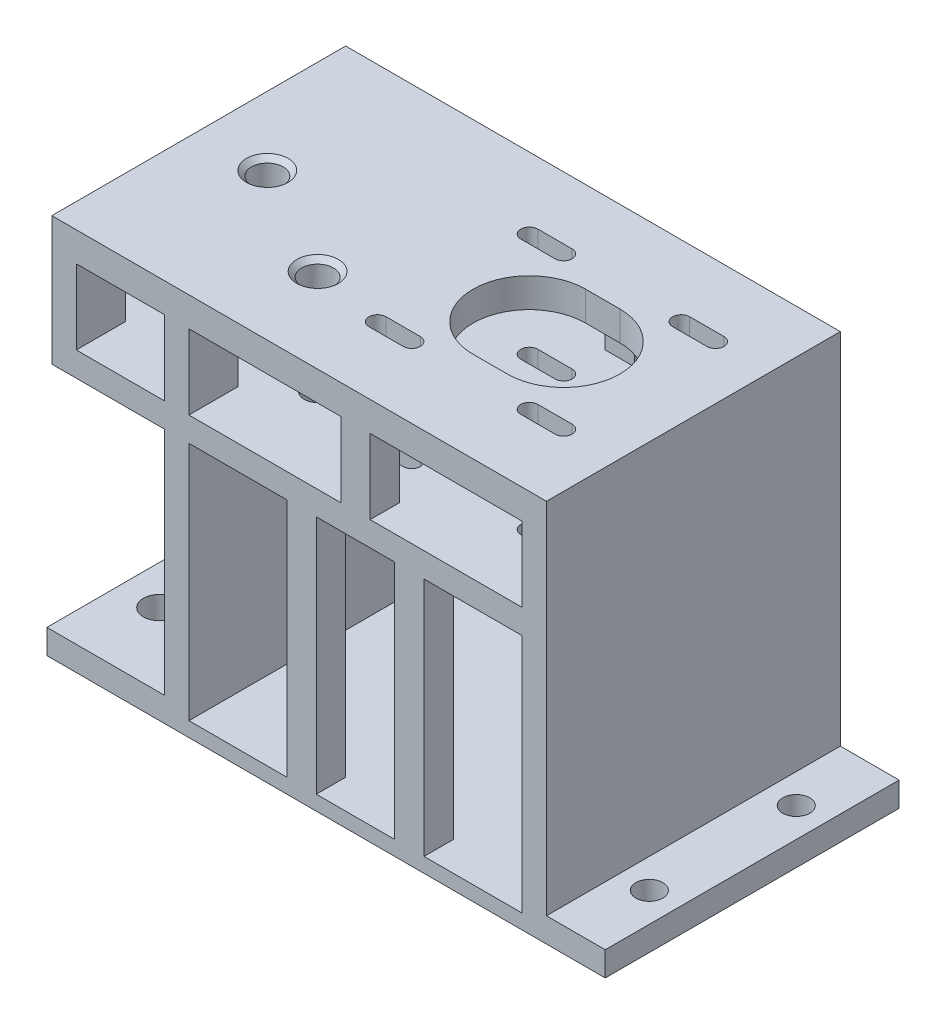
SolidWorks part; units mm, degrees
material "PET"
ref_plane "Front Plane" through (0, 0, 0) normal (0, 0, 1) x (1, 0, 0)
ref_plane "Top Plane" through (0, 0, 0) normal (0, 1, 0) x (1, 0, 0)
ref_plane "Right Plane" through (0, 0, 0) normal (1, 0, 0) x (0, 0, -1)
sketch "Sketch1" plane through (0, 0, 0) normal (0, 0, 1) x (1, 0, 0)
  line L0 (85, 0) -> (-29, 0)
  line L1 (-29, 0) -> (-29, 5)
  line L2 (-29, 5) -> (-5, 5)
  line L3 (-5, 5) -> (-5, 52.05)
  line L6 (-28, 78.3) -> (73, 78.3)
  line L7 (73, 78.3) -> (73, 5)
  line L11 (68, 3) -> (68, 52.05)
  line L12 (68, 72.3) -> (0, 72.3)
  line L13 (0, 72.3) -> (0, 57.05)
  line L14 (0, 57.05) -> (68, 57.05)
  line L16 (68, 52.05) -> (0, 52.05)
  line L17 (0, 3) -> (0, 52.05)
  line L19 (-28, 78.3) -> (-28, 52.05)
  line L20 (-28, 52.05) -> (-5, 52.05)
  line L21 (-5, 72.3) -> (-23, 72.3)
  line L22 (-23, 72.3) -> (-23, 57.05)
  line L23 (-23, 57.05) -> (-5, 57.05)
  line L25 (-5, 57.05) -> (-5, 72.3)
  line L28 (68, 57.05) -> (68, 72.3)
  line L29 (73, 5) -> (85, 5)
  line L30 (85, 5) -> (85, 0)
  line L31 (0, 3) -> (68, 3)
  point P19 (0, 27.525)
  point P28 (-29, 2.5)
  dimension "D1" = 5
  dimension "D2" = 6
  dimension "D3" = 5
  dimension "D4" = 5
  dimension "D5" = 5
  dimension "D6" = 15.25
  dimension "D7" = 57.05
  dimension "D8" = 101
  dimension "D9" = 5
  dimension "D10" = 12
  dimension "D11" = 3
  dimension "D13" = 23
  dimension "D14" = 5
  dimension "D15" = 5
  dimension "D16" = 24
extrude "Boss-Extrude1" add sketch "Sketch1" along normal blind 60
sketch "Sketch2" plane through (0, 0, 0) normal (1, 0, 0) x (0, 0, -1)
  line L0 (-60, 5) -> (-60, 78.3) construction
  line L1 (-50, 72.3) -> (-10, 72.3)
  line L2 (-50, 72.3) -> (-50, 57.05)
  line L3 (-50, 57.05) -> (-10, 57.05)
  line L4 (-10, 72.3) -> (-10, 57.05)
  line L5 (-60, 78.3) -> (0, 78.3) construction
  line L6 (0, 5) -> (0, 78.3) construction
  dimension "D1" = 10
  dimension "D2" = 15.25
  dimension "D3" = 6
  dimension "D4" = 10
extrude "Cut-Extrude1" cut sketch "Sketch2" against normal through all
sketch "Sketch3" plane through (0, 78.3, 0) normal (0, 1, 0) x (1, 0, 0)
  line L0 (18, -30) -> (68, -30) construction
  line L2 (73, -60) -> (73, 0) construction
  line L3 (39.5, -30) -> (46.5, -30) construction
  line L4 (39.5, -18.5) -> (46.5, -18.5)
  line L5 (39.5, -41.5) -> (46.5, -41.5)
  line L6 (31, -14.5) -> (24, -14.5) construction
  line L7 (31, -16.25) -> (24, -16.25)
  line L8 (31, -12.75) -> (24, -12.75)
  line L9 (43, -30) -> (43, 0) construction
  line L10 (73, -60) -> (-28, -60) construction
  line L12 (73, 0) -> (-28, 0) construction
  line L13 (55, -14.5) -> (62, -14.5) construction
  line L14 (55, -16.25) -> (62, -16.25)
  line L15 (55, -12.75) -> (62, -12.75)
  line L16 (31, -45.5) -> (24, -45.5) construction
  line L17 (31, -43.75) -> (24, -43.75)
  line L18 (31, -47.25) -> (24, -47.25)
  line L19 (55, -45.5) -> (62, -45.5) construction
  line L20 (55, -43.75) -> (62, -43.75)
  line L21 (55, -47.25) -> (62, -47.25)
  arc A0 (39.5, -18.5) -> (39.5, -41.5) centre (39.5, -30) ccw
  arc A1 (46.5, -41.5) -> (46.5, -18.5) centre (46.5, -30) ccw
  arc A2 (31, -16.25) -> (31, -12.75) centre (31, -14.5) ccw
  arc A3 (24, -12.75) -> (24, -16.25) centre (24, -14.5) ccw
  arc A4 (55, -16.25) -> (55, -12.75) centre (55, -14.5) cw
  arc A5 (62, -12.75) -> (62, -16.25) centre (62, -14.5) cw
  arc A6 (31, -43.75) -> (31, -47.25) centre (31, -45.5) cw
  arc A7 (24, -47.25) -> (24, -43.75) centre (24, -45.5) cw
  arc A8 (55, -43.75) -> (55, -47.25) centre (55, -45.5) ccw
  arc A9 (62, -47.25) -> (62, -43.75) centre (62, -45.5) ccw
  point P8 (43, -30)
  point P15 (27.5, -14.5)
  point P24 (58.5, -14.5)
  point P31 (27.5, -45.5)
  point P38 (58.5, -45.5)
  dimension "D2" = 11.5
  dimension "D4" = 1.75
  dimension "D1" = 7
  dimension "D3" = 7
  dimension "D5" = 15.5
  dimension "D6" = 15.5
  dimension "D7" = 5
  dimension "D8" = 55
  dimension "D9" = 30
extrude "Cut-Extrude2" cut sketch "Sketch3" against normal up to surface (26.25 mm away) up to face at (34, 52.05, 30)
sketch "Sketch5" plane through (0, 78.3, 0) normal (0, 1, 0) x (1, 0, 0)
  line L0 (73, -30) -> (-28, -30) construction
  line L4 (73, -60) -> (73, 0) construction
  line L5 (-28, -60) -> (-28, 0) construction
  circle A0 centre (9, -42.73) radius 3.25
  dimension "D1" = 6.5
  dimension "D3" = 64
  dimension "D2" = 12.73
extrude "Cut-Extrude3" cut sketch "Sketch5" against normal up to next
sketch "Sketch6" plane through (0, 57.05, 0) normal (0, 1, 0) x (1, 0, 0)
  circle A0 centre (9, -42.73) radius 2.75
  dimension "D1" = 5.5
extrude "Cut-Extrude4" cut sketch "Sketch6" against normal up to next
sketch "Sketch7" plane through (0, 78.3, 0) normal (0, 1, 0) x (1, 0, 0)
  line L0 (28, -30) -> (-29, -30) construction
  line L3 (-29, -60) -> (-29, 0) construction
  line L4 (-28, -60) -> (-28, 0) construction
  arc A0 (39.5, -18.5) -> (39.5, -41.5) centre (39.5, -30) ccw construction
  circle A1 centre (-14, -30) radius 2.75
  dimension "D1" = 14
  dimension "D2" = 5.5
extrude "Cut-Extrude5" cut sketch "Sketch7" against normal through all
sketch "Sketch8" plane through (0, 78.3, 0) normal (0, 1, 0) x (1, 0, 0)
  circle A0 centre (-14, -30) radius 3.25
  dimension "D1" = 6.5
extrude "Cut-Extrude6" cut sketch "Sketch8" against normal up to next
chamfer "Chamfer1" distance 1 angle 45 2 edges at (-14, 78.3, 33.25) (9, 78.3, 45.98)
ref_plane "Plane1" through (9, 0, 0) normal (1, 0, 0) x (0, 0, -1)
sketch "Sketch10" plane through (0, 0, 0) normal (0, -1, 0) x (1, 0, 0)
  line L0 (-21, 60) -> (-21, 0) construction
  line L1 (-29, 60) -> (85, 60) construction
  line L2 (-29, 0) -> (85, 0) construction
  line L3 (79, 60) -> (79, 0) construction
  line L6 (0, 60) -> (0, 0) construction
  line L7 (-21, 45) -> (79, 45) construction
  line L8 (-29, 30) -> (85, 30) construction
  line L9 (-29, 60) -> (-29, 0) construction
  line L11 (-21, 15) -> (79, 15) construction
  line L13 (85, 60) -> (85, 0) construction
  line L14 (-29, 0) -> (85, 0) construction
  line L15 (-29, 60) -> (85, 60) construction
  circle A0 centre (-21, 45) radius 3.3
  circle A1 centre (-21, 15) radius 3.3
  circle A2 centre (79, 15) radius 2.75
  circle A3 centre (79, 45) radius 2.75
  dimension "D5" = 6.6
  dimension "D6" = 6.6
  dimension "D7" = 5.5
  dimension "D8" = 5.5
  dimension "D1" = 21
  dimension "D2" = 15
  dimension "D3" = 15
  dimension "D4" = 6
extrude "Cut-Extrude8" cut sketch "Sketch10" against normal up to next
sketch "Sketch11" plane through (0, 52.05, 0) normal (0, -1, 0) x (1, 0, 0)
  line L0 (0, 60) -> (0, 0) construction
  line L1 (0, 38) -> (18.5, 38)
  line L2 (0, 38) -> (0, 22)
  line L3 (0, 22) -> (18.5, 22)
  line L4 (18.5, 38) -> (18.5, 22)
  line L5 (73, 30) -> (-28, 30) construction
  dimension "D1" = 5.5
  dimension "D2" = 8
  dimension "D3" = 16
extrude "Boss-Extrude2" add sketch "Sketch11" along normal blind 12
sketch "Sketch12" plane through (18.5, 0, 0) normal (1, 0, 0) x (0, 0, -1)
  line L0 (-38, 40.05) -> (-22, 52.05) construction
  circle A0 centre (-29.334, 46.5495) radius 3.25
  dimension "D1" = 6.5
extrude "Cut-Extrude9" cut sketch "Sketch12" against normal through all
chamfer "Chamfer2" distance 1 angle 45 1 edges at (-5, 46.5495, 26.084)
sketch "Sketch13" plane through (0, 0, 60) normal (0, 0, 1) x (1, 0, 0)
  line L0 (0, 57.05) -> (68, 57.05) construction
  line L1 (31, 72.3) -> (37, 72.3)
  line L2 (31, 72.3) -> (31, 57.05)
  line L3 (31, 57.05) -> (37, 57.05)
  line L4 (37, 72.3) -> (37, 57.05)
  dimension "D1" = 6
extrude "Boss-Extrude3" add sketch "Sketch13" against normal blind 6
sketch "Sketch14" plane through (0, 0, 60) normal (0, 0, 1) x (1, 0, 0)
  line L0 (68, 52.05) -> (0, 52.05) construction
  line L1 (20, 52.05) -> (26, 52.05)
  line L2 (20, 52.05) -> (20, 3)
  line L3 (20, 3) -> (26, 3)
  line L4 (26, 52.05) -> (26, 3)
  line L5 (0, 3) -> (68, 3) construction
  line L6 (0, 52.05) -> (0, 3) construction
  line L7 (42, 52.05) -> (48, 52.05)
  line L8 (42, 52.05) -> (42, 3)
  line L9 (42, 3) -> (48, 3)
  line L10 (48, 52.05) -> (48, 3)
  line L11 (68, 3) -> (68, 52.05) construction
  dimension "D1" = 6
  dimension "D2" = 6
  dimension "D3" = 20
  dimension "D4" = 20
extrude "Boss-Extrude4" add sketch "Sketch14" against normal blind 6
sketch "Sketch15" plane through (0, 0, 0) normal (0, 0, -1) x (-1, 0, 0)
  line L1 (-26, 52.05) -> (-20, 52.05)
  line L2 (-26, 52.05) -> (-26, 3)
  line L3 (-26, 3) -> (-20, 3)
  line L4 (-20, 52.05) -> (-20, 3)
  line L5 (-37, 57.05) -> (-31, 57.05)
  line L6 (-37, 57.05) -> (-37, 72.3)
  line L7 (-37, 72.3) -> (-31, 72.3)
  line L8 (-31, 57.05) -> (-31, 72.3)
extrude "Boss-Extrude5" add sketch "Sketch15" against normal blind 6
sketch "Sketch16" plane through (0, 0, 0) normal (0, 0, -1) x (-1, 0, 0)
  line L0 (28, 52.05) -> (5, 29.05)
  line L1 (5, 52.05) -> (5, 5) construction
  line L2 (5, 29.05) -> (5, 52.05)
  line L3 (5, 52.05) -> (28, 52.05)
  dimension "D1" = 45
extrude "Boss-Extrude6" add sketch "Sketch16" against normal up to surface (10 mm away) up to face at (-25.5, 64.675, 10)
